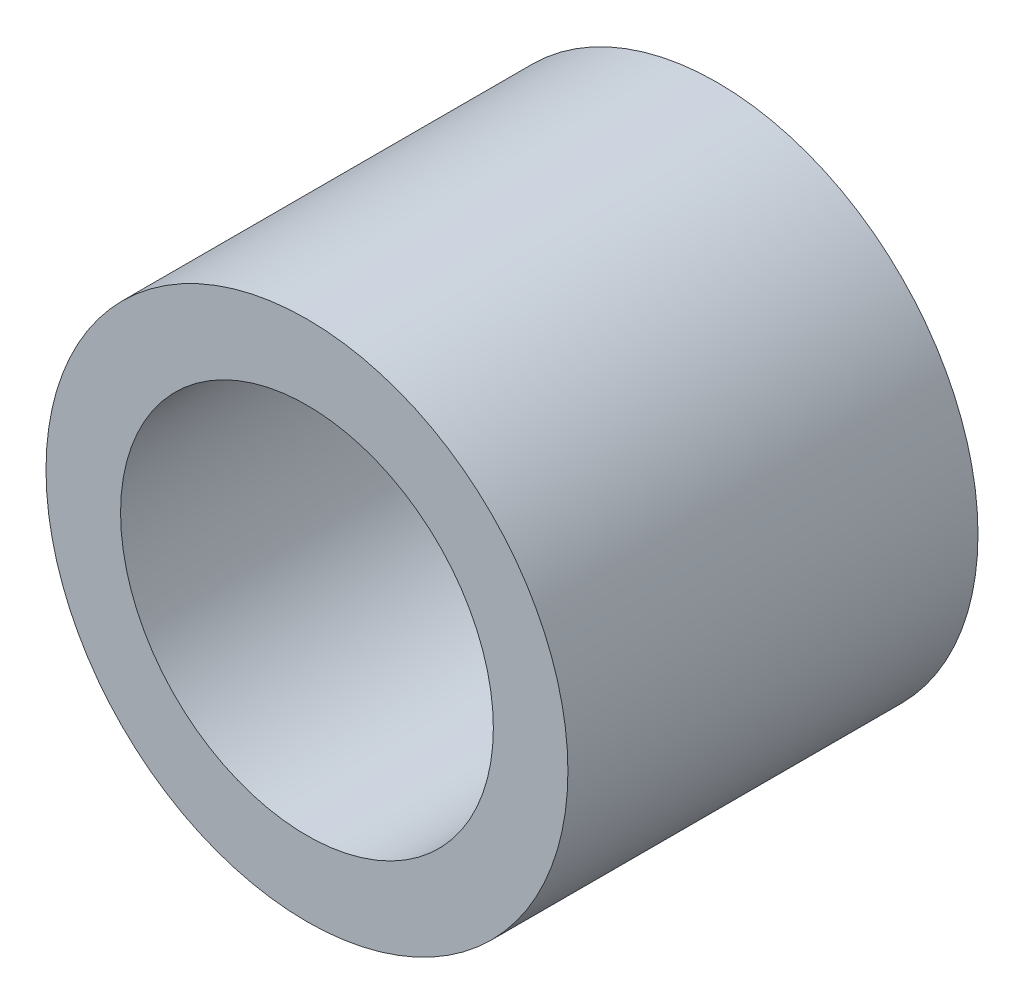
SolidWorks part; units mm, degrees
material "ABS"
ref_plane "Front Plane" through (0, 0, 0) normal (0, 0, 1) x (1, 0, 0)
ref_plane "Top Plane" through (0, 0, 0) normal (0, 1, 0) x (1, 0, 0)
ref_plane "Right Plane" through (0, 0, 0) normal (1, 0, 0) x (0, 0, -1)
sketch "Sketch1" plane through (0, 0, 0) normal (0, 0, 1) x (1, 0, 0)
  circle A4 centre (0, 0) radius 3.175
  circle A5 centre (0, 0) radius 4.445
  dimension "D1" = 6.35
  dimension "D2" = 1.27
extrude "Boss-Extrude1" add sketch "Sketch1" along normal blind 6.985
